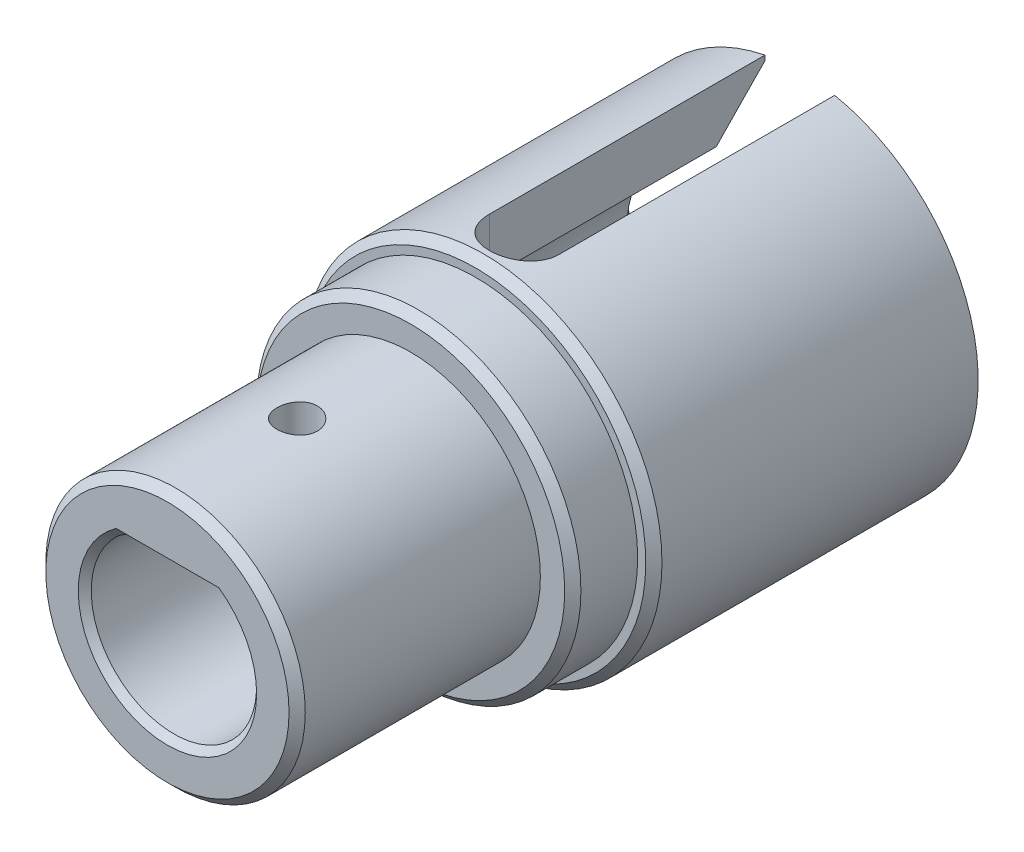
SolidWorks part; units mm, degrees
material "7075-O (SS)"
ref_plane "前视基准面" through (0, 0, 0) normal (0, 0, 1) x (1, 0, 0)
ref_plane "上视基准面" through (0, 0, 0) normal (0, 1, 0) x (1, 0, 0)
ref_plane "右视基准面" through (0, 0, 0) normal (1, 0, 0) x (0, 0, -1)
sketch "草图1" plane through (0, 0, 0) normal (0, 0, 1) x (1, 0, 0)
  circle A0 centre (0, 0) radius 11
  dimension "D1" = 22
extrude "凸台-拉伸1" add sketch "草图1" along normal blind 29
sketch "草图2" plane through (0, 0, 29) normal (0, 0, 1) x (1, 0, 0)
  circle A0 centre (0, 0) radius 10
  dimension "D1" = 20
extrude "切除-拉伸1" cut sketch "草图2" against normal blind 9 flip side to cut
sketch "草图3" plane through (0, 0, 0) normal (0, 0, -1) x (-1, 0, 0)
  circle A0 centre (0, 0) radius 7.7
  dimension "D1" = 15.4
extrude "切除-拉伸2" cut sketch "草图3" against normal blind 20
sketch "草图4" plane through (0, 0, 0) normal (0, 1, 0) x (1, 0, 0)
  line L0 (-2.15, -17) -> (-2.15, 0)
  line L1 (11, 0) -> (-11, 0) construction
  line L2 (2.15, -17) -> (2.15, 0)
  line L3 (7.7, 0) -> (-7.7, 0) construction
  line L4 (2.15, 0) -> (-2.15, 0)
  circle A0 centre (0, -17) radius 2.15
  dimension "D2" = 4.3
  dimension "D1" = 17
extrude "切除-拉伸3" cut sketch "草图4" against normal mid plane 50 contours A0 L2 L4 L0 | A0 region at (0, 0, 7.6632) region at (0, 0, 17)
chamfer "倒角1" distance 3 angle 45 2 edges at (7.7, 0, 0) (-7.7, 0, 0)
sketch "草图5" plane through (0, 0, 29) normal (0, 0, 1) x (1, 0, 0)
  circle A1 centre (0, 0) radius 10
  circle A2 centre (0, 0) radius 10
  dimension "D1" = 0
extrude "凸台-拉伸2" add sketch "草图5" along normal blind 10
sketch "草图6" plane through (0, 0, 39) normal (0, 0, 1) x (1, 0, 0)
  line L0 (-3, 4) -> (3, 4)
  circle A0 centre (0, 0) radius 5
  dimension "D1" = 10
  dimension "D2" = 4
extrude "切除-拉伸5" cut sketch "草图6" against normal up to surface (19 mm away) contours L0 A0 region at (0, -0.2418, 39) up to face at (-7.7, 0, 20)
sketch "草图7" plane through (0, 0, 39) normal (0, 0, 1) x (1, 0, 0)
  line L3 (3.0332, 4.1) -> (-3.0332, 4.1)
  line L4 (3.0332, 4.1) -> (-3.0332, 4.1)
  arc A2 (-3.0332, 4.1) -> (3.0332, 4.1) centre (0, 0) ccw
  arc A3 (-3.0332, 4.1) -> (3.0332, 4.1) centre (0, 0) ccw
  dimension "D1" = 0.1
extrude "切除-拉伸6" cut sketch "草图7" against normal up to surface (19 mm away) up to face at (-7.7, 0, 20)
sketch "草图8" plane through (0, 0, 39) normal (0, 0, 1) x (1, 0, 0)
  circle A0 centre (0, 0) radius 8
  dimension "D1" = 16
extrude "切除-拉伸7" cut sketch "草图8" against normal blind 15 flip side to cut
sketch "草图9" plane through (0, 0, 0) normal (0, 1, 0) x (1, 0, 0)
  line L0 (-8, -39) -> (8, -39) construction
  circle A0 centre (0, -31) radius 1
  dimension "D1" = 8
  dimension "D2" = 2
extrude "切除-拉伸8" cut sketch "草图9" against normal mid plane 50
hole_wizard "M3 螺纹孔1" positions "3D草图2" profile "草图11" tap size "M3" standard "GB"
sketch3d "3D草图2"
  circle A0 centre (0, 4.1, 31) radius 1.25
  spline S0 degree 3 poles (-0.2645, 8, 32) (0.1323, 8, 32) (0.262, 7.9966, 31.9739) (0.5042, 7.985, 31.8735) (0.615, 7.9769, 31.7992) (0.7993, 7.9605, 31.6149) (0.8738, 7.9523, 31.5034) (0.9736, 7.9407, 31.2628) (0.9999, 7.9373, 31.1311) (1.0001, 7.9372, 30.87) (0.9742, 7.9406, 30.7389) (0.8739, 7.9523, 30.4966) (0.8006, 7.9604, 30.3865) (0.6141, 7.9769, 30.1998) (0.5041, 7.985, 30.1265) (0.262, 7.9966, 30.0261) (0.131, 8, 30) (-0.1302, 8, 30) (-0.2619, 7.9966, 30.0262) (-0.5027, 7.9851, 30.1258) (-0.6142, 7.9769, 30.2001) (-0.7987, 7.9606, 30.3843) (-0.873, 7.9524, 30.495) (-0.9737, 7.9407, 30.7371) (-0.9999, 7.9373, 30.8668) (-1.0001, 7.9372, 31.1313) (-0.9741, 7.9406, 31.2612) (-0.8739, 7.9523, 31.5034) (-0.7997, 7.9605, 31.6143) (-0.5235, 7.985, 31.891) (-0.2645, 8, 32) (0.1323, 8, 32) (0.262, 7.9966, 31.9739) knots -0.125 -0.125 0 0 0.0625 0.0625 0.125 0.125 0.1875 0.1875 0.25 0.25 0.3125 0.3125 0.375 0.375 0.4375 0.4375 0.5 0.5 0.5625 0.5625 0.625 0.625 0.6875 0.6875 0.75 0.75 0.8125 0.8125 0.875 0.875 1 1 1.0625 1.0625 1.125 only from (0, 8, 32) to (0, 8, 32) construction
  spline S1 degree 3 poles (-0.2645, 8, 32) (0.1323, 8, 32) (0.262, 7.9966, 31.9739) (0.5042, 7.985, 31.8735) (0.615, 7.9769, 31.7992) (0.7993, 7.9605, 31.6149) (0.8738, 7.9523, 31.5034) (0.9736, 7.9407, 31.2628) (0.9999, 7.9373, 31.1311) (1.0001, 7.9372, 30.87) (0.9742, 7.9406, 30.7389) (0.8739, 7.9523, 30.4966) (0.8006, 7.9604, 30.3865) (0.6141, 7.9769, 30.1998) (0.5041, 7.985, 30.1265) (0.262, 7.9966, 30.0261) (0.131, 8, 30) (-0.1302, 8, 30) (-0.2619, 7.9966, 30.0262) (-0.5027, 7.9851, 30.1258) (-0.6142, 7.9769, 30.2001) (-0.7987, 7.9606, 30.3843) (-0.873, 7.9524, 30.495) (-0.9737, 7.9407, 30.7371) (-0.9999, 7.9373, 30.8668) (-1.0001, 7.9372, 31.1313) (-0.9741, 7.9406, 31.2612) (-0.8739, 7.9523, 31.5034) (-0.7997, 7.9605, 31.6143) (-0.5235, 7.985, 31.891) (-0.2645, 8, 32) (0.1323, 8, 32) (0.262, 7.9966, 31.9739) knots -0.125 -0.125 0 0 0.0625 0.0625 0.125 0.125 0.1875 0.1875 0.25 0.25 0.3125 0.3125 0.375 0.375 0.4375 0.4375 0.5 0.5 0.5625 0.5625 0.625 0.625 0.6875 0.6875 0.75 0.75 0.8125 0.8125 0.875 0.875 1 1 1.0625 1.0625 1.125 only from (0, 8, 32) to (0, 8, 32) construction
  point P8 (0, 4.1, 31)
  point P10 (0, 5.35, 31)
  dimension "D1" = 8
  dimension "D2" = 2.5
sketch "草图11" plane through (0, 4.1, 31) normal (1, 0, 0) x (0, 0, -1)
  line L0 (0, 0) -> (0, 8.2511)
  line L1 (0, 8.2511) -> (1.25, 7.5)
  line L2 (1.25, 7.5) -> (1.25, 0)
  line L5 (1.25, 0) -> (0, 0)
  line L10 (0, 8.2511) -> (-1.25, 7.5) construction
  line L11 (0, -6.35) -> (0, 107.95) construction
  dimension "螺纹孔钻头直径" = 2.5
  dimension "螺纹孔钻头深度" = 7.5
  dimension "导头角度" = 118
cosmetic thread "孔螺蚊线1" parameters "D1"=4.9, "D2"=3
mirror "镜向1" about plane through (0, 0, 0) normal (0, 1, 0) of "M3 螺纹孔1"
chamfer "倒角2" distance 0.4 angle 45 2 edges at (0, 4.1, 39) (0, -5.1, 39)
chamfer "倒角3" distance 0.5 angle 45 3 edges at (10, 0, 24) (11, 0, 20) (8, 0, 39)
fillet "圆角1" radius 1.5 2 edges at (3.0332, 4.1, 29.3) (-3.0332, 4.1, 29.3)
